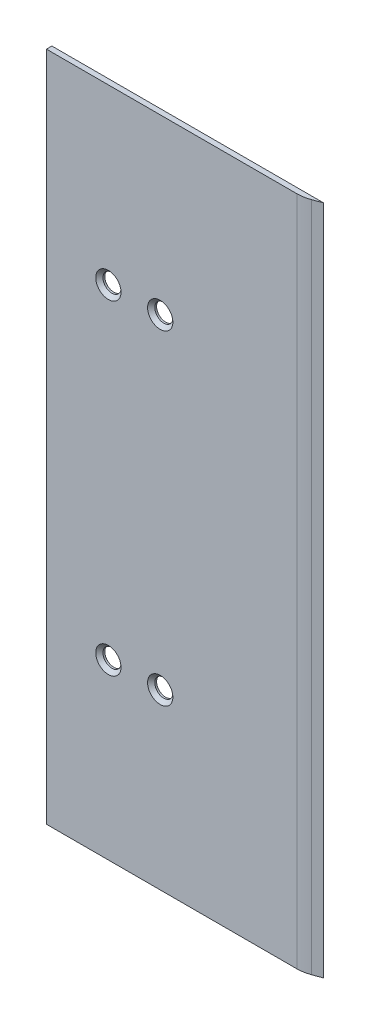
SolidWorks part; units mm, degrees
ref_plane "Front Plane" through (0, 0, 0) normal (0, 0, 1) x (1, 0, 0)
ref_plane "Top Plane" through (0, 0, 0) normal (0, 1, 0) x (1, 0, 0)
ref_plane "Right Plane" through (0, 0, 0) normal (1, 0, 0) x (0, 0, -1)
sketch "Esquisse1" plane through (0, 0, 0) normal (0, 0, 1) x (1, 0, 0)
  line L0 (-30.677, 138) -> (47.9128, 138) construction
  line L1 (47.9128, -48) -> (-27.3702, -48)
  line L2 (47.9128, -48) -> (47.9128, 138)
  line L3 (47.9128, 138) -> (-27.3702, 138)
  line L4 (-27.3702, -48) -> (-27.3702, 138)
  line L5 (-27.3702, 138) -> (-27.3702, -48) construction
  circle A0 centre (-10.2071, 90) radius 2.5
  circle A1 centre (4.1532, 90) radius 2.5
  circle A2 centre (-10.2071, 0) radius 2.5
  circle A3 centre (4.1532, 0) radius 2.5
extrude "Boss.-Extru.1" add sketch "Esquisse1" along normal blind 1.5
chamfer "Chanfrein3" distance 1.5 angle 70 1 edges at (47.9128, 45, 1.5) first distance on face at (47.9128, 45, 0.75)
fillet "Congé2" radius 10 1 edges at (43.7916, 45, 1.5)
chamfer "Chanfrein4" distance 1 angle 45 4 edges at (6.6532, 90, 1.5) (-7.7071, 0, 1.5) (6.6532, 0, 1.5) (-7.7071, 90, 1.5)
